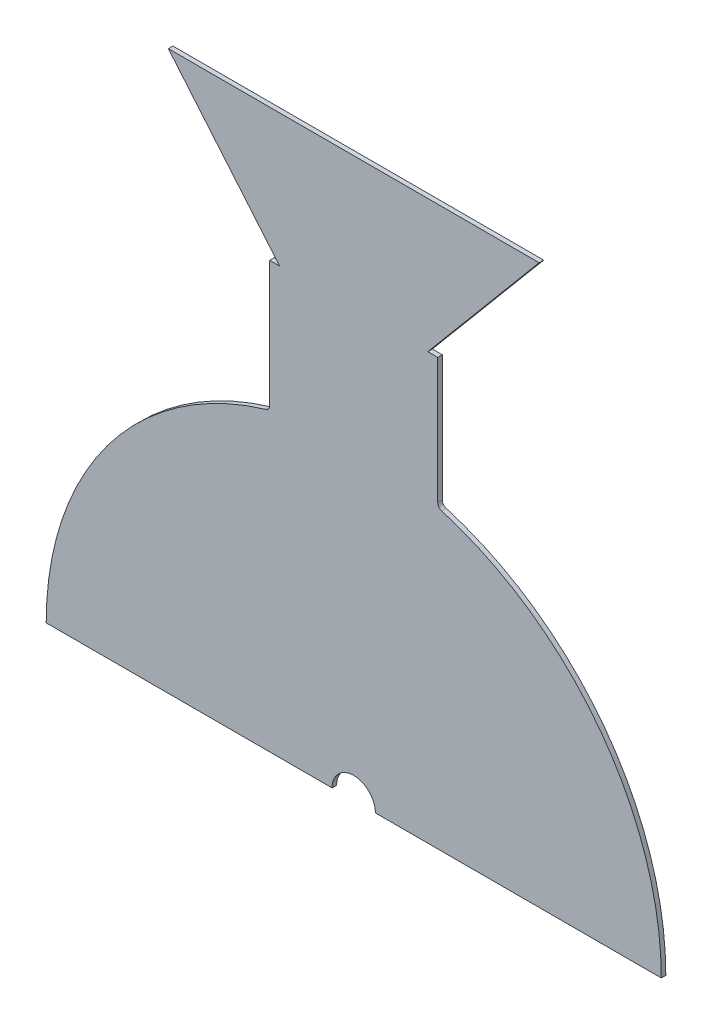
SolidWorks part; units mm, degrees
ref_plane "Front Plane" through (0, 0, 0) normal (0, 0, 1) x (1, 0, 0)
ref_plane "Top Plane" through (0, 0, 0) normal (0, 1, 0) x (1, 0, 0)
ref_plane "Right Plane" through (0, 0, 0) normal (1, 0, 0) x (0, 0, -1)
sketch "Sketch1" plane through (0, 0, 0) normal (0, 0, 1) x (1, 0, 0)
  line L0 (-180.4568, 0) -> (-12.7, 0)
  line L1 (0, 0) -> (0, 199.7416) construction
  line L3 (-49.2912, 0) -> (-12.7, 0) construction
  line L4 (-49.2912, 0) -> (-49.2912, 173.5945) construction
  line L5 (-49.2912, 173.5945) -> (49.2912, 173.5945) construction
  line L6 (49.2912, 0) -> (49.2912, 173.5945) construction
  line L9 (-49.2912, 173.5945) -> (-49.2912, 249.7945)
  line L10 (-49.2912, 249.7945) -> (-114.5985, 327.6246) construction
  line L11 (-108.7959, 327.6246) -> (108.7959, 327.6246)
  line L15 (49.2912, 173.5945) -> (49.2912, 249.7945)
  line L16 (49.2912, 249.7945) -> (114.5985, 327.6246) construction
  line L17 (-12.7, 0) -> (0, 0) construction
  line L18 (12.7, 0) -> (180.4568, 0)
  line L19 (-12.7, 0) -> (0, 0) construction
  line L20 (0, 0) -> (49.2912, 0) construction
  line L21 (-108.7959, 327.6246) -> (-43.4887, 249.7945)
  line L22 (-43.4887, 249.7945) -> (43.4887, 249.7945) construction
  line L23 (43.4887, 249.7945) -> (108.7959, 327.6246)
  line L24 (-43.4887, 249.7945) -> (-49.2912, 249.7945)
  line L25 (43.4887, 249.7945) -> (49.2912, 249.7945)
  line L26 (-114.5985, 327.6246) -> (-108.7959, 327.6246) construction
  line L27 (108.7959, 327.6246) -> (114.5985, 327.6246) construction
  arc A0 (-180.4568, 0) -> (-49.2912, 173.5945) centre (0, 0) cw
  arc A1 (49.2912, 173.5945) -> (180.4568, 0) centre (0, 0) cw
  arc A2 (-12.7, 0) -> (12.7, 0) centre (0, 0) cw
  point P9 (0, 173.5945)
  point P21 (0, 327.6246)
  dimension "D2" = 180.4568
  dimension "D9" = 12.7
  dimension "D1" = 98.5825
  dimension "D3" = 77.8301
  dimension "D4" = 76.2
  dimension "D5" = 101.6
  dimension "D7" = 4.445
base flange "Base-Flange1" sketch "Sketch1" thickness 2.6568 reverse thickness direction no parameters "D1"=0.7366
fillet "Fillet1" radius 3.175 2 edges at (49.2912, 173.5945, -1.3284) (-49.2912, 173.5945, -1.3284)
sketch "Bend-Lines1" [suppressed] plane through (0, 0, 0) normal (0, 1, 0) x (1, 0, 0)
sketch "Bounding-Box1" [suppressed] plane through (0, 0, 0) normal (0, 1, 0) x (1, 0, 0)
sheet metal parameters "Sheet-Metal1" thickness 2.6568 parameters "D1"=0.7366
flat pattern "Flat-Pattern1" [suppressed]
sketch "Bend-Lines2" plane through (0, 0, 0) normal (0, 0, 1) x (1, 0, 0)
sketch3d "Bounding-Box2" [suppressed]
  line L0 (-180.4568, 0, 0) -> (180.4568, 0, 0) construction
  line L1 (-180.4568, 327.6246, 0) -> (180.4568, 327.6246, 0) construction
  line L2 (-180.4568, 0, 0) -> (-180.4568, 327.6246, 0) construction
  line L3 (180.4568, 0, 0) -> (180.4568, 327.6246, 0) construction
